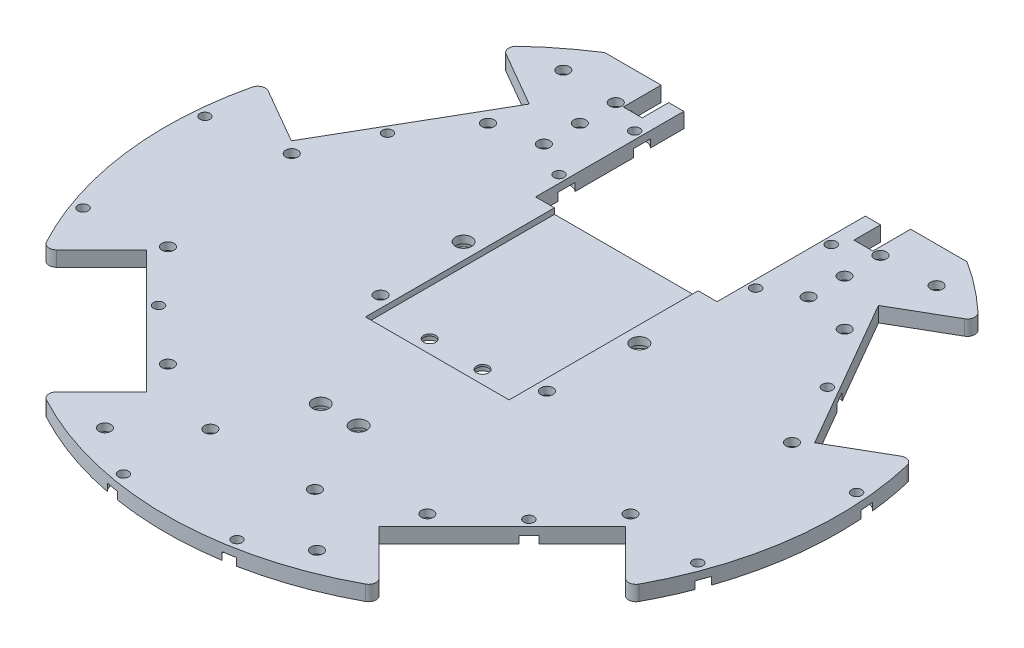
SolidWorks part; units mm, degrees
ref_plane "Front Plane" through (0, 0, 0) normal (0, 0, 1) x (1, 0, 0)
ref_plane "Top Plane" through (0, 0, 0) normal (0, 1, 0) x (1, 0, 0)
ref_plane "Right Plane" through (0, 0, 0) normal (1, 0, 0) x (0, 0, -1)
sketch "Sketch1" plane through (0, 0, 0) normal (0, 1, 0) x (1, 0, 0)
  line L0 (0, 0) -> (57.7211, 33.3253) construction
  line L1 (0, 0) -> (-57.625, 33.2698) construction
  line L2 (0, 0) -> (47.1058, -47.1058) construction
  line L3 (0, 0) -> (-47.0424, -47.0424) construction
  line L4 (0, 0) -> (0, 75) construction
  line L5 (0, 75) -> (47.9166, 75)
  line L6 (0, 75) -> (-47.9166, 75)
  line L7 (57.7211, 33.3253) -> (46.2009, 53.2788)
  line L8 (57.7211, 33.3253) -> (69.229, 13.3931)
  line L9 (-57.625, 33.2698) -> (-46.104, 53.2247)
  line L10 (-57.625, 33.2698) -> (-69.1303, 13.342)
  line L11 (47.1058, -47.1058) -> (30.8201, -63.3916)
  line L12 (47.1058, -47.1058) -> (63.3847, -30.827)
  line L13 (-47.0424, -47.0424) -> (-63.3112, -30.7737)
  line L14 (-47.0424, -47.0424) -> (-30.7835, -63.3014)
  line L15 (-63.3112, -30.7737) -> (-75.1908, -42.6533)
  line L16 (-30.7835, -63.3014) -> (-42.6661, -75.184)
  line L17 (30.8201, -63.3916) -> (42.6312, -75.2027)
  line L18 (63.3847, -30.827) -> (75.1979, -42.6402)
  line L19 (46.2009, 53.2788) -> (60.6358, 61.6128)
  line L20 (69.229, 13.3931) -> (83.6703, 21.7307)
  line L21 (-69.1303, 13.342) -> (-83.669, 21.736)
  line L22 (-46.104, 53.2247) -> (-60.6346, 61.614)
  arc A0 (-86.6154, 20.4638) -> (-78.3661, -42.1871) centre (0, 0) ccw
  arc A1 (61.0067, 64.8011) -> (47.9166, 75) centre (0, 0) ccw
  arc A2 (78.3733, -42.1737) -> (86.6167, 20.4584) centre (0, 0) ccw
  arc A3 (-42.2002, -78.3591) -> (42.1645, -78.3783) centre (0, 0) ccw
  arc A4 (-47.9166, 75) -> (-61.0055, 64.8023) centre (0, 0) ccw
  arc A5 (60.6358, 61.6128) -> (61.0067, 64.8011) centre (59.6358, 63.3449) ccw
  arc A6 (83.6703, 21.7307) -> (86.6167, 20.4584) centre (84.6703, 19.9987) cw
  arc A7 (75.1979, -42.6402) -> (78.3733, -42.1737) centre (76.6121, -41.226) ccw
  arc A8 (42.6312, -75.2027) -> (42.1645, -78.3783) centre (41.217, -76.617) cw
  arc A9 (-42.6661, -75.184) -> (-42.2002, -78.3591) centre (-41.2519, -76.5982) ccw
  arc A10 (-75.1908, -42.6533) -> (-78.3661, -42.1871) centre (-76.6051, -41.2391) cw
  arc A11 (-83.669, 21.736) -> (-86.6154, 20.4638) centre (-84.669, 20.0039) ccw
  arc A12 (-60.6346, 61.614) -> (-61.0055, 64.8023) centre (-59.6346, 63.346) cw
  point P27 (62.9285, 62.9365)
  point P32 (77.0695, -44.5118)
  point P37 (-44.537, -77.0549)
  dimension "D1" = 2
extrude "Boss-Extrude1" add sketch "Sketch1" along normal blind 4
sketch "Sketch2" plane through (0, 4, 0) normal (0, 1, 0) x (1, 0, 0)
  line L0 (-33, 75) -> (33, 75)
  line L1 (47.9166, 75) -> (-47.9166, 75) construction
  line L2 (-33, 75) -> (-33, 69)
  line L3 (33, 75) -> (33, 69)
  line L4 (-33, 69) -> (-28, 69)
  line L5 (33, 69) -> (28, 69)
  line L6 (-28, 69) -> (-28, 72)
  line L7 (28, 69) -> (28, 72)
  line L8 (-28, 72) -> (-24, 72)
  line L9 (28, 72) -> (24, 72)
  line L10 (-24, 72) -> (-24, 32.8)
  line L11 (24, 72) -> (24, 32.8)
  line L12 (-24, 32.8) -> (24, 32.8)
  point P4 (0, 75)
  line M3 (47.9166, 75) -> (-47.9166, 75)
extrude "Cut-Extrude1" cut sketch "Sketch2" against normal blind 4 contours L10 L12 L11 L9 L7 L5 L3 L2 L4 L6 L8 M3 region at (0, 4, -54.6378)
sketch "Sketch3" plane through (0, 4, 0) normal (0, 1, 0) x (1, 0, 0)
  line L0 (-24, 32.8) -> (24, 32.8) construction
  line L1 (-19, 32.8) -> (19, 32.8)
  line L2 (-19, 32.8) -> (-19, -17.2)
  line L3 (-19, -17.2) -> (19, -17.2)
  line L4 (19, 32.8) -> (19, -17.2)
  point P6 (0, 32.8)
  dimension "D1" = 50
  dimension "D2" = 38
extrude "Cut-Extrude2" cut sketch "Sketch3" against normal blind 1.5
chamfer "Chamfer1" distance 4 angle 45 2 edges at (30.5, 4, -69) (-30.5, 4, -69)
hole_wizard "CBORE for M2.5 Pan Head Machine Screw1" positions "3DSketch2" profile "Sketch5" counterbore size "M2.5" standard "ANSI Metric" end condition through all
sketch3d "3DSketch2"
  line L0 (24, 0, -72) -> (24, 0, -32.8) construction
  line L1 (-24, 0, -32.8) -> (24, 0, -32.8) construction
  line L2 (-24, 0, -72) -> (-24, 0, -32.8) construction
  point P0 (26, 0, -61)
  point P2 (26, 0, -41)
  point P4 (-26, 0, -61)
  point P6 (-26, 0, -41)
  dimension "D1" = 20
  dimension "D2" = 2
  dimension "D3" = 8.2
  dimension "D4" = 2
sketch "Sketch5" plane through (26, 0, -61) normal (1, 0, 0) x (0, 0, -1)
  line L0 (0, 0) -> (0, 4)
  line L1 (0, 4) -> (1.35, 4)
  line L3 (1.35, 4) -> (1.35, 2.1)
  line L4 (1.35, 2.1) -> (3, 2.1)
  line L5 (3, 2.1) -> (3, 0)
  line L7 (3, 0) -> (0, 0)
  line L11 (0, -6.35) -> (0, 107.95) construction
  dimension "Thru Hole Dia." = 2.7
  dimension "Thru Hole Depth" = 4
  dimension "C'Bore Dia." = 6
  dimension "C'Bore Depth" = 2.1
sketch "Sketch6" plane through (0, 0, 0) normal (0, -1, 0) x (-1, 0, 0)
  line L0 (0, 0) -> (49.3488, 65.4881) construction
  line L1 (0, 0) -> (-49.3488, 65.4881) construction
  line L2 (0, 0) -> (28.0457, -77.0548) construction
  line L3 (0, 0) -> (-28.0457, -77.0548) construction
hole_wizard "CBORE for M3 Pan Head Machine Screw5" positions "3DSketch3" profile "Sketch7" counterbore size "M3" standard "ANSI Metric" end condition through all
sketch3d "3DSketch3"
  point P0 (49.3488, 0, -65.4881)
  point P3 (-49.3488, 0, -65.4881)
  point P6 (-28.0457, 0, 77.0548)
  point P9 (28.0457, 0, 77.0548)
sketch "Sketch7" plane through (49.3488, 0, -65.4881) normal (1, 0, 0) x (0, 0, -1)
  line L0 (0, 0) -> (0, 4)
  line L1 (0, 4) -> (1.6, 4)
  line L3 (1.6, 4) -> (1.6, 2)
  line L4 (1.6, 2) -> (3, 2)
  line L5 (3, 2) -> (3, 0)
  line L7 (3, 0) -> (0, 0)
  line L11 (0, -6.35) -> (0, 107.95) construction
  dimension "Thru Hole Dia." = 3.2
  dimension "Thru Hole Depth" = 4
  dimension "C'Bore Dia." = 6
  dimension "C'Bore Depth" = 2
hole_wizard "CBORE for M3 Pan Head Machine Screw1" positions "3DSketch4" profile "Sketch8" counterbore size "M3" standard "ANSI Metric" end condition through all
sketch3d "3DSketch4"
  line L0 (24, 0, -72) -> (24, 0, -63.2361) construction
  line L1 (47.9166, 0, -75) -> (33, 0, -75) construction
  line L2 (-24, 0, -72) -> (-24, 0, -63.2361) construction
  point P0 (35, 0, -65)
  point P2 (35, 0, -55.5)
  point P4 (35, 0, -46)
  point P18 (-35, 0, -65)
  point P20 (-35, 0, -55.5)
  point P22 (-35, 0, -46)
  dimension "D1" = 11
  dimension "D2" = 10
  dimension "D3" = 9.5
  dimension "D4" = 9.5
  dimension "D5" = 11
sketch "Sketch8" plane through (35, 0, -65) normal (1, 0, 0) x (0, 0, -1)
  line L0 (0, 0) -> (0, 4)
  line L1 (0, 4) -> (1.6, 4)
  line L3 (1.6, 4) -> (1.6, 2)
  line L4 (1.6, 2) -> (3, 2)
  line L5 (3, 2) -> (3, 0)
  line L7 (3, 0) -> (0, 0)
  line L11 (0, -6.35) -> (0, 107.95) construction
  dimension "Thru Hole Dia." = 3.2
  dimension "Thru Hole Depth" = 4
  dimension "C'Bore Dia." = 6
  dimension "C'Bore Depth" = 2
sketch "Sketch9" plane through (0, 0, 0) normal (0, -1, 0) x (-1, 0, 0)
  line L0 (66.1662, 10.476) -> (47.1662, 43.385) construction
  line L1 (61.1898, -27.2381) -> (34.3198, -54.1082) construction
  line L2 (69.1303, 13.342) -> (83.669, 21.736) construction
  line L3 (75.1908, -42.6533) -> (63.3112, -30.7737) construction
  line L4 (46.104, 53.2247) -> (69.1303, 13.342) construction
  line L5 (63.3112, -30.7737) -> (30.7835, -63.3014) construction
  line L6 (56.6662, 26.9305) -> (55.7912, 28.446) construction
  line L7 (47.7548, -40.6731) -> (48.9923, -41.9106) construction
  line L8 (56.6662, 26.9305) -> (58.1817, 27.8055) construction
  line L9 (0, 32.8) -> (0.0202, -89) construction
  line L10 (24, 32.8) -> (-24, 32.8) construction
  arc A0 (-42.1645, -78.3783) -> (42.2002, -78.3591) centre (0, 0) ccw construction
  point P24 (-48.9674, -41.9269)
  point P25 (-61.1699, -27.2585)
  point P26 (-34.2909, -54.1196)
  point P27 (-66.1587, 10.454)
  point P28 (-47.1697, 43.3693)
  point P29 (-58.18, 27.7861)
  dimension "D1" = 1
  dimension "D2" = 38
  dimension "D3" = 1
  dimension "D4" = 38
  dimension "D5" = 4
  dimension "D6" = 4
hole_wizard "CBORE for M3 Pan Head Machine Screw2" positions "3DSketch5" profile "Sketch10" counterbore size "M3" standard "ANSI Metric" end condition through all
sketch3d "3DSketch5"
  point P0 (47.1697, 0, -43.3693)
  point P3 (66.1587, 0, -10.454)
  point P6 (61.1699, 0, 27.2585)
  point P9 (34.2909, 0, 54.1196)
  point P12 (-34.3198, 0, 54.1082)
  point P15 (-61.1898, 0, 27.2381)
  point P18 (-66.1662, 0, -10.476)
  point P21 (-47.1662, 0, -43.385)
sketch "Sketch10" plane through (47.1697, 0, -43.3693) normal (1, 0, 0) x (0, 0, -1)
  line L0 (0, 0) -> (0, 4)
  line L1 (0, 4) -> (1.6, 4)
  line L3 (1.6, 4) -> (1.6, 2)
  line L4 (1.6, 2) -> (3, 2)
  line L5 (3, 2) -> (3, 0)
  line L7 (3, 0) -> (0, 0)
  line L11 (0, -6.35) -> (0, 107.95) construction
  dimension "Thru Hole Dia." = 3.2
  dimension "Thru Hole Depth" = 4
  dimension "C'Bore Dia." = 6
  dimension "C'Bore Depth" = 2
hole_wizard "CBORE for M2.5 Pan Head Machine Screw3" positions "3DSketch6" profile "Sketch11" counterbore size "M2.5" standard "ANSI Metric" end condition through all
sketch3d "3DSketch6"
  point P0 (58.18, 0, -27.7861)
  point P3 (-58.1817, 0, -27.8055)
  point P6 (-48.9923, 0, 41.9106)
  point P9 (48.9674, 0, 41.9269)
sketch "Sketch11" plane through (58.18, 0, -27.7861) normal (1, 0, 0) x (0, 0, -1)
  line L0 (0, 0) -> (0, 4)
  line L1 (0, 4) -> (1.35, 4)
  line L3 (1.35, 4) -> (1.35, 2)
  line L4 (1.35, 2) -> (3, 2)
  line L5 (3, 2) -> (3, 0)
  line L7 (3, 0) -> (0, 0)
  line L11 (0, -6.35) -> (0, 107.95) construction
  dimension "Thru Hole Dia." = 2.7
  dimension "Thru Hole Depth" = 4
  dimension "C'Bore Dia." = 6
  dimension "C'Bore Depth" = 2
sketch "Sketch12" plane through (0, 0, 0) normal (0, -1, 0) x (-1, 0, 0)
  line L0 (0, 32.8) -> (0.0202, -89) construction
  line L1 (24, 32.8) -> (-24, 32.8) construction
  arc A0 (-42.1645, -78.3783) -> (42.2002, -78.3591) centre (0, 0) ccw construction
  point P0 (23.2533, 13)
  point P1 (5.0126, -43)
  point P9 (-4.9874, -43.0017)
  point P10 (-23.2467, 12.9923)
  dimension "D1" = 23.25
  dimension "D2" = 5
  dimension "D3" = 19.8
  dimension "D4" = 75.8
hole_wizard "CBORE for M4 Pan Head Machine Screw1" positions "3DSketch7" profile "Sketch13" counterbore size "M4" standard "ANSI Metric" end condition through all
sketch3d "3DSketch7"
  point P0 (23.2467, 0, -12.9923)
  point P3 (-23.2533, 0, -13)
  point P6 (-5.0126, 0, 43)
  point P9 (4.9874, 0, 43.0017)
sketch "Sketch13" plane through (23.2467, 0, -12.9923) normal (1, 0, 0) x (0, 0, -1)
  line L0 (0, 0) -> (0, 4)
  line L1 (0, 4) -> (2.15, 4)
  line L3 (2.15, 4) -> (2.15, 2)
  line L4 (2.15, 2) -> (4, 2)
  line L5 (4, 2) -> (4, 0)
  line L7 (4, 0) -> (0, 0)
  line L11 (0, -6.35) -> (0, 107.95) construction
  dimension "Thru Hole Dia." = 4.3
  dimension "Thru Hole Depth" = 4
  dimension "C'Bore Dia." = 8
  dimension "C'Bore Depth" = 2
sketch "Sketch14" plane through (0, 0, 0) normal (0, -1, 0) x (-1, 0, 0)
  line L0 (0, 0) -> (-86.1708, 7.539) construction
  line L1 (0, 0) -> (86.1708, 7.539) construction
  line L2 (0, 0) -> (-81.2834, -29.5847) construction
  line L3 (0, 0) -> (81.2834, -29.5847) construction
  line L4 (0, 0) -> (-15.0206, -85.1859) construction
  line L5 (0, 0) -> (15.0206, -85.1859) construction
  circle A0 centre (0, 0) radius 86.5 construction
hole_wizard "CBORE for M2.5 Pan Head Machine Screw4" positions "3DSketch8" profile "Sketch15" counterbore size "M2.5" standard "ANSI Metric" end condition through all
sketch3d "3DSketch8"
  point P0 (86.1708, 0, -7.539)
  point P3 (81.2834, 0, 29.5847)
  point P6 (15.0206, 0, 85.1859)
  point P9 (-15.0206, 0, 85.1859)
  point P12 (-81.2834, 0, 29.5847)
  point P15 (-86.1708, 0, -7.539)
sketch "Sketch15" plane through (86.1708, 0, -7.539) normal (1, 0, 0) x (0, 0, -1)
  line L0 (0, 0) -> (0, 4)
  line L1 (0, 4) -> (1.35, 4)
  line L3 (1.35, 4) -> (1.35, 2)
  line L4 (1.35, 2) -> (3, 2)
  line L5 (3, 2) -> (3, 0)
  line L7 (3, 0) -> (0, 0)
  line L11 (0, -6.35) -> (0, 107.95) construction
  dimension "Thru Hole Dia." = 2.7
  dimension "Thru Hole Depth" = 4
  dimension "C'Bore Dia." = 6
  dimension "C'Bore Depth" = 2
sketch "Sketch16" plane through (0, 0, 0) normal (0, -1, 0) x (-1, 0, 0)
  line L1 (19, -17.2) -> (-19, -17.2) construction
  line L2 (-19, 32.8) -> (-19, -17.2) construction
  line L3 (0, 0) -> (0, -89) construction
  arc A0 (-13.7955, -87.9243) -> (13.7955, -87.9243) centre (0, 0) ccw construction
  point P0 (-22, -10.2)
  point P1 (-13.8201, -63.3916)
  point P6 (13.8201, -63.3916)
  point P14 (22, -10.2)
  dimension "D1" = 7
  dimension "D2" = 3
  dimension "D3" = 17
hole_wizard "CBORE for M3 Pan Head Machine Screw3" positions "3DSketch9" profile "Sketch17" counterbore size "M3" standard "ANSI Metric" end condition through all
sketch3d "3DSketch9"
  point P0 (22, 0, 10.2)
  point P3 (-22, 0, 10.2)
  point P6 (-13.8201, 0, 63.3916)
  point P9 (13.8201, 0, 63.3916)
sketch "Sketch17" plane through (22, 0, 10.2) normal (1, 0, 0) x (0, 0, -1)
  line L0 (0, 0) -> (0, 4)
  line L1 (0, 4) -> (1.6, 4)
  line L3 (1.6, 4) -> (1.6, 2)
  line L4 (1.6, 2) -> (3, 2)
  line L5 (3, 2) -> (3, 0)
  line L7 (3, 0) -> (0, 0)
  line L11 (0, -6.35) -> (0, 107.95) construction
  dimension "Thru Hole Dia." = 3.2
  dimension "Thru Hole Depth" = 4
  dimension "C'Bore Dia." = 6
  dimension "C'Bore Depth" = 2
sketch "Sketch18" plane through (0, 0, 0) normal (0, -1, 0) x (-1, 0, 0)
  line L0 (0, 32.8) -> (0, -21.0643) construction
  line L1 (24, 32.8) -> (-24, 32.8) construction
  line L2 (19, -17.2) -> (-19, -17.2) construction
  point P5 (7, -12.2)
  point P6 (-7, -12.2)
  dimension "D1" = 5
  dimension "D2" = 7
hole_wizard "CBORE for M3 Pan Head Machine Screw4" positions "3DSketch10" profile "Sketch19" counterbore size "M3" standard "ANSI Metric" end condition through all
sketch3d "3DSketch10"
  point P0 (-7, 0, 12.2)
  point P3 (7, 0, 12.2)
sketch "Sketch19" plane through (-7, 0, 12.2) normal (1, 0, 0) x (0, 0, -1)
  line L0 (0, 0) -> (0, 4)
  line L1 (0, 4) -> (1.6, 4)
  line L3 (1.6, 4) -> (1.6, 2)
  line L4 (1.6, 2) -> (3, 2)
  line L5 (3, 2) -> (3, 0)
  line L7 (3, 0) -> (0, 0)
  line L11 (0, -6.35) -> (0, 107.95) construction
  dimension "Thru Hole Dia." = 3.2
  dimension "Thru Hole Depth" = 4
  dimension "C'Bore Dia." = 6
  dimension "C'Bore Depth" = 2
